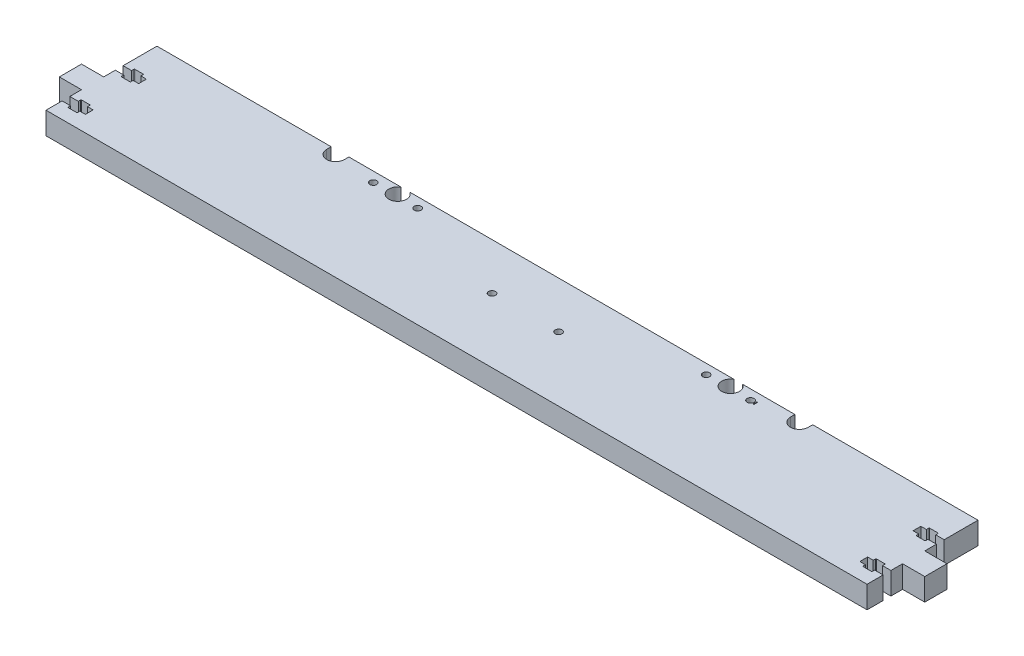
SolidWorks part; units mm, degrees
ref_plane "Front Plane" through (0, 0, 0) normal (0, 0, 1) x (1, 0, 0)
ref_plane "Top Plane" through (0, 0, 0) normal (0, 1, 0) x (1, 0, 0)
ref_plane "Right Plane" through (0, 0, 0) normal (1, 0, 0) x (0, 0, -1)
sketch "Sketch1" plane through (0, 0, 0) normal (0, 1, 0) x (1, 0, 0)
  line L0 (0, 25) -> (0, -25)
  line L1 (-185, 25) -> (0, 25)
  line L2 (-185, 25) -> (-185, -25) construction
  line L3 (-185, -25) -> (0, -25)
  line L4 (-185, -4) -> (-195, -4) construction
  line L5 (-185, 25) -> (0, 0) construction
  line L6 (-185, -25) -> (0, 0) construction
  line L7 (-185, -9) -> (-195, -9)
  line L8 (-195, -9) -> (-195, 1)
  line L9 (-195, 1) -> (-185, 1)
  line L10 (-185, 1) -> (-185, 25)
  line L11 (-185, -9) -> (-185, -25)
  line L47 (0, -25) -> (0, 25) construction
  line L89 (0, -25) -> (0, 25) construction
  point P0 (0, 0)
  dimension "D1" = 185
  dimension "D25" = 25
  dimension "D4" = 50
  dimension "D3" = 21
  dimension "D5" = 10
  dimension "D6" = 10
  dimension "D7" = 5
extrude "MainBody" add sketch "Sketch1" along normal blind 10 contours L3 region at (-93.5428, 0, 0.0428)
sketch "Sketch5" plane through (0, 10, 0) normal (0, 1, 0) x (1, 0, 0)
  line L0 (-185, 8) -> (-174.5, 8) construction
  line L1 (-185, 1) -> (-185, 25) construction
  line L2 (-185, 9.75) -> (-174.5, 9.75) construction
  line L3 (-174.5, 9.75) -> (-174.5, 6.25) construction
  line L4 (-174.5, 6.25) -> (-185, 6.25) construction
  line L5 (-185, 9.75) -> (-181.2, 9.75)
  line L6 (-181.2, 9.75) -> (-181.2, 10.75)
  line L7 (-180.95, 11) -> (-177.25, 11)
  line L8 (-177, 10.75) -> (-177, 9.75)
  line L9 (-177, 9.75) -> (-174.5, 9.75)
  line L10 (-174.5, 9.75) -> (-174.5, 6.25)
  line L11 (-185, 6.25) -> (-185, 9.75)
  line L12 (-195, -9) -> (-195, 1) construction
  line L13 (-185, 6.25) -> (-174.5, 6.25) construction
  line L14 (-177, 6.25) -> (-174.5, 6.25)
  line L15 (-177, 5.25) -> (-177, 6.25)
  line L16 (-180.95, 5) -> (-177.25, 5)
  line L17 (-181.2, 6.25) -> (-181.2, 5.25)
  line L18 (-185, 6.25) -> (-181.2, 6.25)
  line L19 (-185, 1) -> (-185, -9) construction
  line L20 (-195, -4) -> (-185, -4) construction
  line L21 (-195, -9) -> (-195, 1) construction
  line L22 (-185, -14.25) -> (-174.5, -14.25) construction
  line L23 (-174.5, -14.25) -> (-185, -14.25) construction
  line L24 (-174.5, -17.75) -> (-174.5, -14.25) construction
  line L25 (-185, -17.75) -> (-174.5, -17.75) construction
  line L26 (-185, -16) -> (-174.5, -16) construction
  line L27 (-185, -14.25) -> (-181.2, -14.25)
  line L28 (-181.2, -14.25) -> (-181.2, -13.25)
  line L29 (-180.95, -13) -> (-177.25, -13)
  line L30 (-177, -13.25) -> (-177, -14.25)
  line L31 (-177, -14.25) -> (-174.5, -14.25)
  line L32 (-185, -14.25) -> (-185, -17.75)
  line L33 (-174.5, -17.75) -> (-174.5, -14.25)
  line L34 (-177, -17.75) -> (-174.5, -17.75)
  line L35 (-177, -18.75) -> (-177, -17.75)
  line L36 (-180.95, -19) -> (-177.25, -19)
  line L37 (-181.2, -17.75) -> (-181.2, -18.75)
  line L38 (-185, -17.75) -> (-181.2, -17.75)
  line L39 (-185, 6.25) -> (-174.5, 6.25) construction
  arc A0 (-177.25, 11) -> (-177, 10.75) centre (-177.25, 10.75) cw
  arc A1 (-181.2, 10.75) -> (-180.95, 11) centre (-180.95, 10.75) cw
  arc A2 (-181.2, 5.25) -> (-180.95, 5) centre (-180.95, 5.25) ccw
  arc A3 (-177.25, 5) -> (-177, 5.25) centre (-177.25, 5.25) ccw
  arc A4 (-177.25, -13) -> (-177, -13.25) centre (-177.25, -13.25) cw
  arc A5 (-181.2, -13.25) -> (-180.95, -13) centre (-180.95, -13.25) cw
  arc A6 (-181.2, -18.75) -> (-180.95, -19) centre (-180.95, -18.75) ccw
  arc A7 (-177.25, -19) -> (-177, -18.75) centre (-177.25, -18.75) ccw
  point P6 (-195, -4)
  point P17 (-177, 11)
  point P20 (-181.2, 11)
  point P29 (-181.2, 5)
  point P30 (-177, 5)
  point P61 (-177, -13)
  point P62 (-181.2, -13)
  point P63 (-181.2, -19)
  point P64 (-177, -19)
  dimension "D8" = 0.25
  dimension "D1" = 10.5
  dimension "D2" = 1.75
  dimension "D4" = 4.2
  dimension "D5" = 8
  dimension "D6" = 3
  dimension "D7" = 12
extrude "ScrewCutouts" cut sketch "Sketch5" against normal through all
mirror "Mirror1" about plane through (0, 0, 0) normal (1, 0, 0) of "ScrewCutouts", "MainBody"
sketch "Sketch3" plane through (0, 10, 0) normal (0, 1, 0) x (1, 0, 0)
  line L0 (2, 25) -> (2, -25) construction
  line L1 (-185, 25) -> (185, 25) construction
  line L2 (-185, -25) -> (185, -25) construction
  line L3 (-63, 20.5) -> (-83, 20.5) construction
  line L4 (-73, 17.5) -> (-73, 25.5) construction
  line L5 (77, 17.5) -> (77, 25.5) construction
  line L6 (67, 20.5) -> (87, 20.5) construction
  circle A0 centre (-73, 21.5) radius 4
  circle A1 centre (-83, 20.5) radius 1.55
  circle A2 centre (-63, 20.5) radius 1.55
  circle A3 centre (67, 20.5) radius 1.55
  circle A4 centre (87, 20.5) radius 1.55
  circle A5 centre (77, 21.5) radius 4
  dimension "D2" = 8
  dimension "D4" = 3.1
  dimension "D1" = 3.5
  dimension "D5" = 75
  dimension "D6" = 2
  dimension "D3" = 10
  dimension "D7" = 1
extrude "RodCutouts" cut sketch "Sketch3" against normal through all
sketch "Sketch6" plane through (0, 10, 0) normal (0, 1, 0) x (1, 0, 0)
  line L0 (-73, 21.5) -> (77, 21.5) construction
  line L1 (2, 21.5) -> (2, -25) construction
  line L2 (-185, -25) -> (185, -25) construction
  line L3 (17, 4) -> (-13, 4) construction
  line L4 (-71.0635, 25) -> (75.0635, 25) construction
  circle A0 centre (-13, 4) radius 1.55
  circle A1 centre (17, 4) radius 1.55
  point P13 (2, 4)
  dimension "D3" = 21
  dimension "D1" = 3.1
  dimension "D2" = 15
extrude "Cut-Extrude1" cut sketch "Sketch6" against normal through all
sketch "Sketch7" plane through (0, 10, 0) normal (0, 1, 0) x (1, 0, 0)
  line L0 (-73, 21.5) -> (77, 21.5) construction
  line L1 (2, 21.5) -> (2, -25) construction
  line L3 (-102.5, 25) -> (-102.5, 23) construction
  line L4 (-185, 25) -> (-74.9365, 25) construction
  line L5 (-98.5, 25) -> (-98.5, 23)
  line L6 (-106.5, 25) -> (-106.5, 23)
  line L7 (106.5, 25) -> (106.5, 23) construction
  line L8 (102.5, 25) -> (102.5, 23)
  line L9 (110.5, 25) -> (110.5, 23)
  line L12 (-185, -25) -> (185, -25) construction
  arc A0 (-98.5, 25) -> (-106.5, 25) centre (-102.5, 25) ccw
  arc A1 (-106.5, 23) -> (-98.5, 23) centre (-102.5, 23) ccw
  arc A2 (102.5, 25) -> (110.5, 25) centre (106.5, 25) cw
  arc A3 (110.5, 23) -> (102.5, 23) centre (106.5, 23) cw
  point P12 (-102.5, 24)
  point P19 (106.5, 24)
  dimension "D1" = 4
  dimension "D2" = 2
  dimension "D3" = 104.5
extrude "BedAdjustmentScrewCutout" cut sketch "Sketch7" against normal through all
sketch "Sketch8" plane through (0, 10, 0) normal (0, 1, 0) x (1, 0, 0)
  line L0 (88.35, 20.5) -> (89.35, 20.5) construction
  line L1 (88.55, 20.5) -> (88.55, 25) construction
  line L2 (88.35, 20.5) -> (89.35, 21.5)
  line L3 (89.35, 21.5) -> (89.35, 19.5)
  line L4 (88.35, 20.5) -> (89.35, 19.5)
  line L5 (78.9365, 25) -> (102.5, 25) construction
  circle A1 centre (87, 20.5) radius 1.55 construction
  point P9 (89.35, 20.5)
  dimension "D1" = 1
  dimension "D2" = 1
  dimension "D3" = 0.2
extrude "DirectionKey" cut sketch "Sketch8" against normal through all
equation "\"Y-ROD-SPACING\"=75"
equation "\"Y-BED-OFFSET\"=2"
equation "\"T-SLOT-NUT-FILLET-RADIUS\"=0.25"
equation "\"T-SLOT-SCREW-SHAFT-RADIUS\"=1.75"
equation "\"T-SLOT-SCREW-SHAFT-CUTOUT-LENGTH\"=10.5"
equation "\"T-SLOT-NUT-DEPTH\"=4.2"
equation "\"T-SLOT-NUT-WIDTH\"=3"
equation "\"T-SLOT-NUT-END-DISTANCE\"=8"
equation "\"ACRYLIC-TAB-CUTOUT-SIZE\"=\"ACRYLIC-THICKNESS\"+\"ACRYLIC-TAB-TOLERANCE\"*2"
equation "\"ACRYLIC-M3-HOLE\"=3.1"
equation "\"D1@Sketch5\"=\"T-SLOT-SCREW-SHAFT-CUTOUT-LENGTH\""
equation "\"D2@Sketch5\"=\"T-SLOT-SCREW-SHAFT-RADIUS\""
equation "\"D4@Sketch5\"=\"T-SLOT-NUT-DEPTH\""
equation "\"D5@Sketch5\"=\"T-SLOT-NUT-END-DISTANCE\""
equation "\"D6@Sketch5\"=\"T-SLOT-NUT-WIDTH\""
equation "\"D8@Sketch5\"=\"T-SLOT-NUT-FILLET-RADIUS\""
equation "\"D4@Sketch3\"=\"ACRYLIC-M3-HOLE\""
equation "\"D5@Sketch3\"=\"Y-ROD-SPACING\""
equation "\"D6@Sketch3\"=\"Y-BED-OFFSET\""
equation "\"Y-BED-ROD-INSET\"=3.5"
equation "\"D1@Sketch3\"=\"Y-BED-ROD-INSET\""
equation "\"SMOOTHROD-CAP-SCREW-DISTANCE\"=20"
equation "\"D3@Sketch3\"=\"SMOOTHROD-CAP-SCREW-DISTANCE\"/2"
equation "\"ACRYLIC-TAB-WIDTH\"=\"ACRYLIC-THICKNESS\""
equation "\"FRAME-WIDTH-INNER\"=370"
equation "\"D6@Sketch1\"=\"ACRYLIC-TAB-WIDTH\""
equation "\"D5@Sketch1\"=\"ACRYLIC-TAB-WIDTH\""
equation "\"D1@Sketch1\"=\"FRAME-WIDTH-INNER\"/2"
equation "\"X-ROD-SPACING\"=45"
equation "\"Z-ROD-SPACING\"=17.5"
equation "\"ACRYLIC-THICKNESS\"=10"
equation "\"ACRYLIC-THICKNESS2\"=4.5"
equation "\"NEMA17-HOLE-SPACING\"=31"
equation "\"NEMA17-CENTRAL-CUTOUT\"=22.5"
equation "\"Z-BRACKET-REACH\"=55"
equation "\"TOP-BRACKET-SPACING\"=40"
equation "\"SMOOTHROD-X-LENGTH\"=350"
equation "\"SMOOTHROD-Y-LENGTH\"=350"
equation "\"SMOOTHROD-Z-LENGTH\"=350"
equation "\"SMOOTHROD-TIGHTENING-HEADROOM\"=.25"
equation "\"LEADSCREW-Z-LENGTH\"=300"
equation "\"SCREW-LENGTH-FRAME\"=\"ACRYLIC-THICKNESS\" + 10"
equation "\"SCREW-HEAD-RADIUS\"=6"
equation "\"PRINTED-X-SMOOTHROD-DIAMETER\"=8.2"
equation "\"PRINTED-X-SMOOTHROD-CUTOUT\"=10"
equation "\"PRINTED-X-BASE-HEIGHT\"=10"
equation "\"PRINTED-LM8UU-CUTOUT-SIZE\"=15.25"
equation "\"PRINTED-LM8UU-CUTOUT-LENGTH\"=24.5"
equation "\"PRINTED-X-IDLER-HEIGHT\"=16"
equation "\"PSU-MOUNTING-WIDTH\"=95"
equation "\"PSU-MOUNTING-HEIGHT\"=177"
equation "\"D1@MainBody\"=\"ACRYLIC-THICKNESS\""
equation "\"D7@Sketch1\"=\"ACRYLIC-TAB-WIDTH\"/2"
equation "\"D1@Sketch6\"=\"ACRYLIC-M3-HOLE\""
equation "\"Y-BELT-TO-ROD-DISTANCE\"=20"
equation "\"Y-BED-SCREW-SPACING\"=209"
equation "\"Z-ROD-INSET\"=16"
equation "\"SPOOL-HOLDER-ROD-SPACING\"=150"
equation "\"D3@Sketch7\"=\"Y-BED-SCREW-SPACING\"/2"
equation "\"Y-BED-SCREW-CUTOUT-SLOT-HEIGHT\"=2"
equation "\"D2@Sketch7\"=\"Y-BED-SCREW-CUTOUT-SLOT-HEIGHT\""
equation "\"ACRYLIC-TAB-TOLERANCE\"=.1"
equation "\"SCREW-LENGTH-MOTOR\"=\"ACRYLIC-THICKNESS\" + 5"
equation "\"SCREW-LENGTH-EXTRUDER\"=28"
equation "\"PRINTED-M3-HOLE\"=3.5"
equation "\"ACRYLIC-X-CARRIAGE-WIDTH\"=55"
equation "\"ACRYLIC-X-CARRIAGE-HEIGHT\"=75"
equation "\"ACRYLIC-X-CARRIAGE-LM8UU-CUTOUT-WIDTH\"=24.25"
equation "\"ACRYLIC-X-CARRIAGE-LM8UU-CUTOUT-HEIGHT\"=11.5"
equation "\"ACRYLIC-X-CARRIAGE-SCREW-SPACING-X\"=15"
equation "\"ACRYLIC-X-CARRIAGE-SCREW-SPACING-Y\"=33"
equation "\"ACRYLIC-X-CARRIAGE-CENTER-TAB-SPACING\"=14"
equation "\"ACRYLIC-X-CARRIAGE-EXTRUDER-OFFSET\"=26"
equation "\"ACRYLIC-X-CARRIAGE-EXTRUDER-ANGLE\"=90"
equation "\"ACRYLIC-X-CARRIAGE-EXTRUDER-SHELF-DEPTH\"=\"ACRYLIC-X-CARRIAGE-EXTRUDER-OFFSET\" + 28"
equation "\"ACRYLIC-X-CARRIAGE-EXTRUDER-BRACE-SPACING\"=23"
equation "\"ACRYLIC-X-CARRIAGE-EXTRUDER-BRACE-TAB-OFFSET\"=20"
equation "\"ACRYLIC-X-CARRIAGE-EXTRUDER-BRACE-HEIGHT\"=35"
equation "\"ACRYLIC-X-CARRIAGE-EXTRUDER-BRACE-SCREW-SPACING\"=22"
equation "\"ACRYLIC-X-CARRIAGE-DUAL-WIDTH-MULTIPLIER\"=1.65"
equation "\"ACRYLIC-X-CARRIAGE-DUAL-HOTEND-SPACING\"=42"
equation "\"ACRYLIC-X-CARRIAGE-DUAL-WIDTH\"=103"
equation "\"ACRYLIC-X-CARRIAGE-DUAL-HOTEND-SEPARATION\"=35"
equation "\"ACRYLIC-X-CARRIAGE-DUAL-MOUNT-PLATE-DEPTH\"=76"
equation "\"ACRYLIC-X-CARRIAGE-DUAL-MOUNT-BRACE-WIDTH\"=45"
equation "\"ACRYLIC-X-CARRIAGE-DUAL-MOUNT-SCREW-WIDTH\"=40"
equation "\"BLOWER-FAN-WIDTH\"=15"
